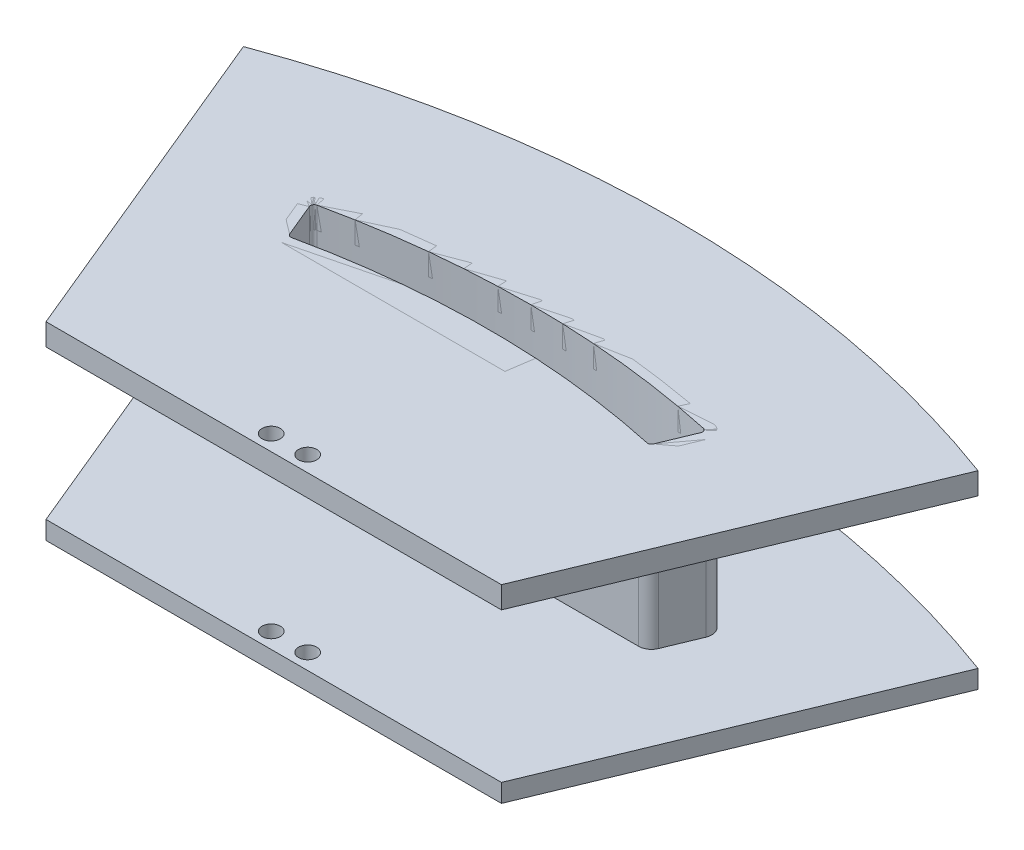
SolidWorks part; units mm, degrees
ref_plane "Front Plane" through (0, 0, 0) normal (0, 0, 1) x (1, 0, 0)
ref_plane "Top Plane" through (0, 0, 0) normal (0, 1, 0) x (1, 0, 0)
ref_plane "Right Plane" through (0, 0, 0) normal (1, 0, 0) x (0, 0, -1)
sketch "Sketch1" plane through (0, 0, 0) normal (0, 1, 0) x (1, 0, 0)
  line L0 (-50.4049, 135.9571) -> (-31.25, 89.7131)
  line L1 (0, 0) -> (0, 192.2134) construction
  line L2 (50.4049, 135.9571) -> (31.25, 89.7131)
  line L3 (-28.7185, 120.7102) -> (-26.8051, 116.0908) construction
  line L4 (28.7185, 120.7102) -> (26.8051, 116.0908) construction
  line L5 (-28.0256, 120.9972) -> (-26.1122, 116.3778)
  line L6 (-24.4954, 115.2975) -> (24.4954, 115.2975)
  line L7 (-26.8707, 121.4755) -> (-24.9573, 116.8561)
  line L8 (26.8707, 121.4755) -> (24.9573, 116.8561)
  line L12 (-31.25, 89.7131) -> (31.25, 89.7131)
  line L13 (-24.4954, 114.5475) -> (24.4954, 114.5475) construction
  line L14 (0, 127) -> (-30.0054, 127) construction
  line L15 (0, 145) -> (-27.091, 145) construction
  line L16 (28.0256, 120.9972) -> (26.1122, 116.3778)
  circle A0 centre (0, 0) radius 145 construction
  arc A1 (-31.25, 89.7131) -> (31.25, 89.7131) centre (0, 0) ccw construction
  arc A2 (-50.4049, 135.9571) -> (50.4049, 135.9571) centre (0, 0) cw
  arc A3 (31.25, 89.7131) -> (5, 94.8683) centre (0, 0) ccw construction
  arc A4 (0, 117.1749) -> (-23.9652, 114.6043) centre (0, 4.1749) ccw construction
  arc A5 (-26.9391, 124.11) -> (26.9391, 124.11) centre (0, 0) cw construction
  arc A6 (-26.1122, 116.3778) -> (-24.4954, 115.2975) centre (-24.4954, 117.0475) ccw
  arc A7 (26.9391, 124.11) -> (28.7185, 120.7102) centre (26.4088, 121.6669) cw construction
  arc A8 (26.1122, 116.3778) -> (24.4954, 115.2975) centre (24.4954, 117.0475) cw
  arc A9 (26.8051, 116.0908) -> (24.4954, 114.5475) centre (24.4954, 117.0475) cw construction
  arc A10 (-26.8051, 116.0908) -> (-24.4954, 114.5475) centre (-24.4954, 117.0475) ccw construction
  arc A11 (-28.7185, 120.7102) -> (-26.9391, 124.11) centre (-26.4088, 121.6669) cw construction
  arc A12 (24.3893, 116.5588) -> (-24.3893, 116.5588) centre (0, 4.1749) ccw
  arc A13 (-24.9573, 116.8561) -> (-24.3893, 116.5588) centre (-24.4954, 117.0475) ccw
  arc A14 (-26.8707, 121.4755) -> (-26.5149, 122.1555) centre (-26.4088, 121.6669) cw
  arc A15 (-26.5149, 122.1555) -> (26.5149, 122.1555) centre (0, 0) cw
  arc A16 (26.5149, 122.1555) -> (26.8707, 121.4755) centre (26.4088, 121.6669) cw
  arc A17 (24.9573, 116.8561) -> (24.3893, 116.5588) centre (24.4954, 117.0475) cw
  arc A18 (0, 95) -> (-5, 94.8683) centre (0, 0) ccw construction
  arc A19 (-5, 94.8683) -> (-31.25, 89.7131) centre (0, 0) ccw construction
  arc A20 (26.78, 123.377) -> (28.0256, 120.9972) centre (26.4088, 121.6669) cw
  arc A21 (0, 95) -> (-5, 94.8683) centre (0, 0) ccw construction
  arc A22 (5, 94.8683) -> (0, 95) centre (0, 0) ccw construction
  arc A23 (5, 94.8683) -> (0, 95) centre (0, 0) ccw construction
  circle A24 centre (-2.5, 91.8683) radius 1.25
  circle A25 centre (2.5, 91.8683) radius 1.25
  arc A26 (-5, 94.8683) -> (-31.25, 89.7131) centre (0, 0) ccw construction
  arc A27 (31.25, 89.7131) -> (5, 94.8683) centre (0, 0) ccw construction
  arc A28 (24.4954, 114.5475) -> (23.9652, 114.6043) centre (24.4954, 117.0475) cw construction
  arc A29 (26.8051, 116.0908) -> (23.9652, 114.6043) centre (24.4954, 117.0475) cw construction
  arc A30 (23.9652, 114.6043) -> (0, 117.1749) centre (0, 4.1749) ccw construction
  arc A31 (23.9652, 114.6043) -> (-23.9652, 114.6043) centre (0, 4.1749) ccw construction
  arc A32 (-24.4954, 114.5475) -> (-23.9652, 114.6043) centre (-24.4954, 117.0475) ccw construction
  arc A33 (-26.8051, 116.0908) -> (-23.9652, 114.6043) centre (-24.4954, 117.0475) ccw construction
  arc A34 (-26.78, 123.377) -> (26.78, 123.377) centre (0, 0) cw
  arc A35 (-28.0256, 120.9972) -> (-26.78, 123.377) centre (-26.4088, 121.6669) cw
  dimension "D1" = 290
  dimension "D2" = 190
  dimension "D4" = 5
  dimension "D5" = 2.5
  dimension "D10" = 2.5
  dimension "D8" = 115
  dimension "D9" = 125
  dimension "D3" = 22.5
  dimension "D7" = 62.5
  dimension "D11" = 45
  dimension "D12" = 0.75
  dimension "D6" = 4.1749
extrude "Boss-Extrude1" add sketch "Sketch1" against normal blind 2.5 contours A25 | L0 L12 L2 A2 | A12 A13 L7 A14 A15 A16 L8 A17 | A24 region at (2.5, 0, -91.8683)
extrude "Boss-Extrude2" add sketch "Sketch1<3>" along normal blind 26 from surface separate body contours A35 L5 A6 L6 A8 L16 A20 A34 L8 A17 A12 A13 L7 A14 A15 A16 region at (-27.451, 0, -122.2123) starting at face at (-2.5, -2.5, -90.6183)
sketch "Sketch1<3>" plane through (0, 0, 0) normal (0, 1, 0) x (1, 0, 0) same geometry as "Sketch1"
extrude "Boss-Extrude3" add sketch "Sketch1<4>" against normal blind 3 from surface contours A35 L5 A6 L6 A8 L16 A20 A34 L8 A17 A12 A13 L7 A14 A15 A16 | A2 L0 L12 L2 A25 A24 L5 A35 A34 A20 L16 A8 L6 A6 region at (0, 0, -143.8502) region at (-27.451, 0, -122.2123) starting at face at (0, 23.5, -119.383)
sketch "Sketch1<4>" plane through (0, 0, 0) normal (0, 1, 0) x (1, 0, 0) same geometry as "Sketch1"
